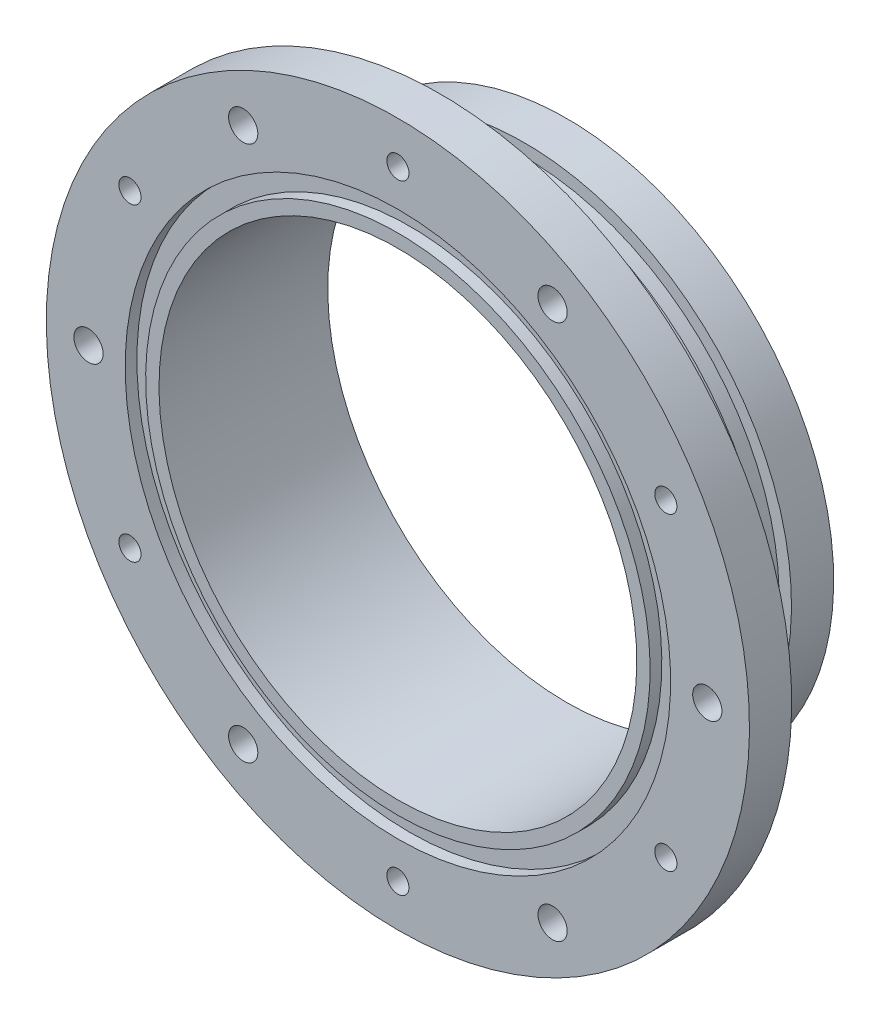
SolidWorks part; units mm, degrees
note: The reader was unsure of these and kept them because the rebuilt part matched: shared geometry of "Sketch1<4>".
material "6061 Alloy"
ref_plane "Front Plane" through (0, 0, 0) normal (0, 0, 1) x (1, 0, 0)
ref_plane "Top Plane" through (0, 0, 0) normal (0, 1, 0) x (1, 0, 0)
ref_plane "Right Plane" through (0, 0, 0) normal (1, 0, 0) x (0, 0, -1)
sketch "Sketch1" plane through (0, 0, 0) normal (1, 0, 0) x (0, 0, -1)
  line L0 (0, 53.9369) -> (0, 56.9468)
  line L1 (0, 79.375) -> (9.525, 79.375)
  line L2 (9.525, 79.375) -> (9.525, 60.2869)
  line L3 (9.525, 60.2869) -> (13.97, 60.2869)
  line L4 (13.97, 60.2869) -> (13.97, 57.5056)
  line L5 (13.97, 57.5056) -> (19.05, 57.5056)
  line L6 (19.05, 57.5056) -> (19.05, 60.2869)
  line L7 (19.05, 60.2869) -> (23.495, 60.2869)
  line L8 (23.495, 60.2869) -> (23.495, 57.5056)
  line L9 (23.495, 57.5056) -> (28.575, 57.5056)
  line L10 (28.575, 57.5056) -> (28.575, 60.2869)
  line L11 (28.575, 60.2869) -> (38.1, 60.2869)
  line L12 (38.1, 60.2869) -> (38.1, 53.9369)
  line L13 (38.1, 53.9369) -> (9.525, 53.9369)
  line L16 (0, 0) -> (38.1, 0) construction
  line L17 (0, 53.9369) -> (9.525, 53.9369)
  line L19 (9.525, 60.325) -> (9.525, 79.375) construction
  line L22 (9.525, 60.325) -> (38.1, 60.325) construction
  line L23 (9.525, 60.325) -> (9.525, 63.5) construction
  line L24 (9.525, 63.5) -> (38.1, 63.5) construction
  line L25 (38.1, 60.325) -> (38.1, 63.5) construction
  line L26 (0, 56.9468) -> (2.6416, 56.9468)
  line L27 (2.6416, 56.9468) -> (2.6416, 61.5696)
  line L28 (2.6416, 61.5696) -> (0, 61.5696)
  line L29 (0, 61.5696) -> (0, 79.375)
  line L30 (0, 56.9468) -> (0, 61.5696)
  line L31 (0, 53.9369) -> (9.525, 53.9369)
  line L32 (0, 53.9369) -> (0, 0)
  line L33 (0, 0) -> (9.525, 0)
  line L34 (9.525, 53.9369) -> (9.525, 0)
  circle A0 centre (25.0825, 59.0931) radius 1.5875 construction
  circle A1 centre (1.0541, 58.5343) radius 1.5875 construction
  circle A2 centre (15.5575, 59.0931) radius 1.5875 construction
  point P32 (15.5575, 0)
  point P33 (1.0541, 0)
  point P34 (25.0825, 0)
  dimension "D7" = 3.175
  dimension "D4" = 6.35
  dimension "D5" = 120.5738
  dimension "D6" = 115.0112
  dimension "D8" = 5.08
  dimension "D9" = 9.525
  dimension "D10" = 9.525
  dimension "D11" = 9.525
  dimension "D2" = 63.5
  dimension "D12" = 3.175
  dimension "D13" = 15.875
  dimension "D3" = 9.525
  dimension "D14" = 2.6416
  dimension "D15" = 113.8936
  dimension "D16" = 4.6228
  dimension "D17" = 0
  dimension "D18" = 3.5687
revolve "Revolve1" add sketch "Sketch1" angle 360 about L16
revolve "Cut-Revolve1" cut sketch "Sketch1<4>" angle 360 about L16
sketch "Sketch1<4>" plane through (0, 0, 0) normal (1, 0, 0) x (0, 0, -1) same geometry as "Sketch1"
sketch "Tapped Holes Sketch" plane through (0, 0, 0) normal (0, 0, 1) x (1, 0, 0)
  circle A0 centre (0, 0) radius 69.85 construction
  point P3 (0, 69.85)
  point P7 (34.925, 60.4919)
  point P8 (60.4919, 34.925)
  point P9 (69.85, 0)
  point P10 (60.4919, -34.925)
  point P11 (34.925, -60.4919)
  point P12 (0, -69.85)
  point P13 (-34.925, -60.4919)
  point P14 (-60.4919, -34.925)
  point P15 (-69.85, 0)
  point P16 (-60.4919, 34.925)
  point P17 (-34.925, 60.4919)
  point P18 (0, 0)
  dimension "D1" = 139.7
  dimension "D2" = 12
hole_wizard "M6 Tapped Hole1" positions "Tapped Holes Sketch" profile "Sketch3" tap size "M6" standard "ISO"
cosmetic thread "Hole Thread2" parameters "D2"=6
cosmetic thread "Hole Thread4" parameters "D2"=6
cosmetic thread "Hole Thread6" parameters "D2"=6
cosmetic thread "Hole Thread8" parameters "D2"=6
cosmetic thread "Hole Thread10" parameters "D2"=6
cosmetic thread "Hole Thread12" parameters "D2"=6
sketch "Sketch3" plane through (-60.4919, 34.925, 0) normal (1, 0, 0) x (0, -1, 0)
  line L0 (0, 0) -> (0, 38.1)
  line L1 (0, 38.1) -> (2.5, 38.1)
  line L2 (2.5, 38.1) -> (2.5, 0)
  line L5 (2.5, 0) -> (0, 0)
  line L11 (0, -6.35) -> (0, 107.95) construction
  dimension "Thru Tap Drill Dia." = 5
  dimension "Thru Tap Drill Depth" = 38.1
sketch "Clearance Holes Sketch" plane through (0, 0, 0) normal (0, 0, 1) x (1, 0, 0)
  line L0 (-60.4919, 34.925) -> (0, 0) construction
  line L1 (0, 0) -> (0, 69.85) construction
  line L2 (0, 0) -> (-34.925, 60.4919) construction
  circle A0 centre (0, 0) radius 69.85 construction
  circle A1 centre (0, 69.85) radius 2.5 construction
  circle A2 centre (0, 69.85) radius 2.5
  circle A3 centre (-60.4919, 34.925) radius 2.5 construction
  circle A4 centre (-60.4919, 34.925) radius 2.5
  point P0 (0, 0)
  point P6 (-34.925, 60.4919)
  point P14 (34.925, 60.4919)
  point P15 (69.85, 0)
  point P16 (34.925, -60.4919)
  point P17 (-34.925, -60.4919)
  point P18 (-69.85, 0)
  point P19 (0, 0)
  dimension "D1" = 30
  dimension "D2" = 6
hole_wizard "M6 Clearance Hole1" positions "Clearance Holes Sketch" profile "Sketch5" hole size "M6" standard "ISO" end condition through all
sketch "Sketch5" plane through (-69.85, 0, 0) normal (1, 0, 0) x (0, -1, 0)
  line L0 (0, 0) -> (0, 38.1)
  line L1 (0, 38.1) -> (3.3, 38.1)
  line L2 (3.3, 38.1) -> (3.3, 0)
  line L5 (3.3, 0) -> (0, 0)
  line L11 (0, -6.35) -> (0, 107.95) construction
  dimension "Thru Hole Dia." = 6.6
  dimension "Thru Hole Depth" = 38.1
ref_point "First O-Ring Point"
ref_point "Second O-Ring Point"
ref_point "Face Seal O-Ring Point"
equation "\"A\"= \"Tube Diameter\" - 0.125 * 2'246 o ring"
equation "\"Tube Diameter\"= 5"
equation "\"C\"= 4.747"
equation "\"B-1\"= 4.528"
equation "\"D5@Sketch1\"=\"C\""
equation "\"D6@Sketch1\"=\"B-1\""
equation "\"W\"= .125"
equation "\"G\"= .2"
equation "\"D8@Sketch1\"=\"G\""
equation "\"D2@Sketch1\"=\"Tube Diameter\"/2"
equation "\"W-face\"= .125"
equation "\"H1-face\"= 4.484'246 o ring"
equation "\"L-face\"= .104"
equation "\"D14@Sketch1\"=\"L-face\""
equation "\"D15@Sketch1\"=\"H1-face\""
equation "\"G-face\"= .182"
equation "\"D16@Sketch1\"=\"G-face\""
